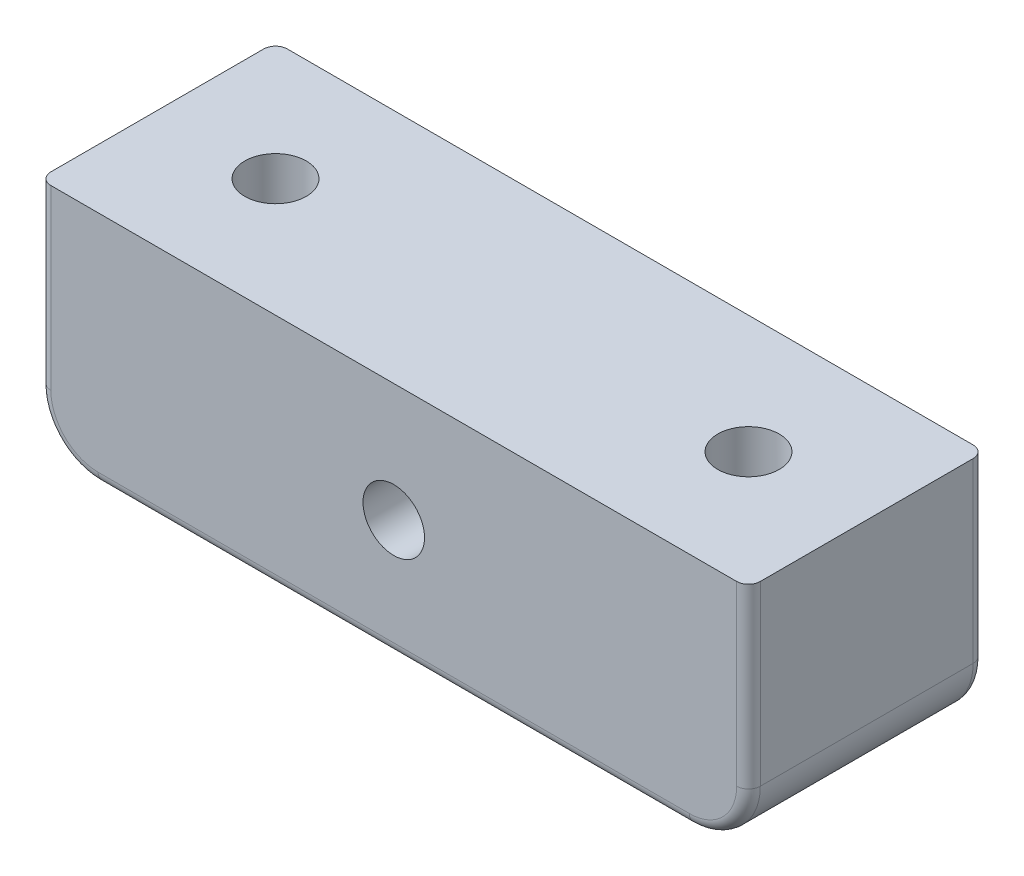
SolidWorks part; units mm, degrees
material "ABS"
ref_plane "Front Plane" through (0, 0, 0) normal (0, 0, 1) x (1, 0, 0)
ref_plane "Top Plane" through (0, 0, 0) normal (0, 1, 0) x (1, 0, 0)
ref_plane "Right Plane" through (0, 0, 0) normal (1, 0, 0) x (0, 0, -1)
sketch "Sketch1" plane through (0, 0, 0) normal (0, 0, 1) x (1, 0, 0)
  line L0 (0, 0) -> (0, -20) construction
  line L1 (-30, 0) -> (30, 0)
  line L2 (-30, 0) -> (-30, -15)
  line L3 (-25, -20) -> (25, -20)
  line L4 (30, 0) -> (30, -15)
  arc A0 (30, -15) -> (25, -20) centre (25, -15) cw
  arc A1 (-25, -20) -> (-30, -15) centre (-25, -15) cw
  circle A2 centre (0, -10) radius 2.6
  point P4 (0, 0)
  point P10 (-30, -20)
  dimension "D3" = 5
  dimension "D4" = 5.2
  dimension "D1" = 20
  dimension "D2" = 60
extrude "Boss-Extrude1" add sketch "Sketch1" along normal blind 20
sketch "Sketch2" plane through (0, 0, 0) normal (0, 1, 0) x (1, 0, 0)
  line L0 (0, 0) -> (0, -20) construction
  line L1 (30, 0) -> (-30, 0) construction
  line L2 (30, -20) -> (-30, -20) construction
  line L3 (0, -10) -> (-30, -10) construction
  line L4 (-30, -20) -> (-30, 0) construction
  circle A0 centre (-20, -10) radius 2.6
  circle A1 centre (20, -10) radius 2.6
  dimension "D1" = 5.2
  dimension "D2" = 20
extrude "Cut-Extrude1" cut sketch "Sketch2" against normal up to surface (20 mm away) up to face at (0, -20, 10)
sketch "Sketch3" plane through (0, 0, 0) normal (0, 0, -1) x (-1, 0, 0)
  line L1 (0, -16.3509) -> (5.5, -13.1754)
  line L2 (5.5, -13.1754) -> (5.5, -6.8246)
  line L3 (5.5, -6.8246) -> (0, -3.6491)
  line L4 (0, -3.6491) -> (-5.5, -6.8246)
  line L5 (-5.5, -6.8246) -> (-5.5, -13.1754)
  line L6 (-5.5, -13.1754) -> (0, -16.3509)
  line L7 (-30, 0) -> (30, 0) construction
  circle A0 centre (0, -10) radius 5.5 construction
  dimension "D1" = 11
extrude "Cut-Extrude2" cut sketch "Sketch3" against normal blind 3
fillet "Fillet1" radius 1 10 edges at (-30, -7.5, 0) (-28.5355, -18.5355, 0) (0, -20, 0) (30, -7.5, 0) (-30, -7.5, 20) (-28.5355, -18.5355, 20) (0, -20, 20) (30, -7.5, 20) (28.5355, -18.5355, 0) (28.5355, -18.5355, 20)
